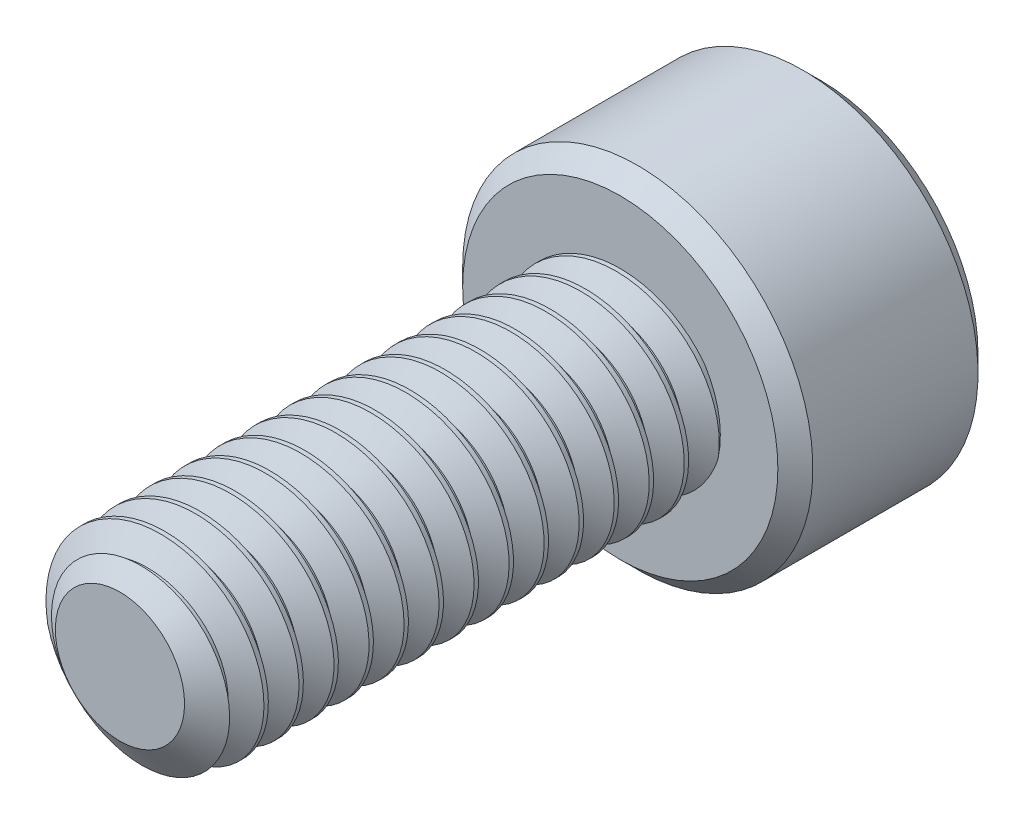
SolidWorks part; units mm, degrees
ref_plane "Front Plane" through (0, 0, 0) normal (0, 0, 1) x (1, 0, 0)
ref_plane "Top Plane" through (0, 0, 0) normal (0, 1, 0) x (1, 0, 0)
ref_plane "Right Plane" through (0, 0, 0) normal (1, 0, 0) x (0, 0, -1)
sketch "Sketch1" plane through (0, 0, 0) normal (0, 0, 1) x (1, 0, 0)
  circle A0 centre (0, 0) radius 2
  dimension "OD" = 4
extrude "Extrude1" add sketch "Sketch1" against normal blind 10
sketch "Sketch2" plane through (0, 0, 0) normal (0, 0, 1) x (1, 0, 0)
  circle A0 centre (0, 0) radius 2 construction
  circle A1 centre (0, 0) radius 2
curve "Helix/Spiral1" pitch 0.7 height 10.7 radius 2 centre (0, 0, 0) axis (0, 0, -1) start towards (0, 1, 0) parameters "pitch"=0.7
sketch "Sketch3" plane through (0, 0, 0) normal (1, 0, 0) x (0, 0, -1)
  line L0 (-0.6125, 2) -> (-0.35, 1.5453)
  line L1 (-0.35, 1.5453) -> (-0.2625, 1.5453)
  line L2 (-0.2625, 1.5453) -> (0, 2)
  line L3 (-0.6125, 2) -> (0, 2)
  line L4 (-0.3063, 2) -> (-0.3063, 1.5453) construction
  line L5 (-0.4813, 1.7727) -> (-0.1313, 1.7727) construction
  line L6 (0, 2) -> (0, -2) construction
  dimension "D1" = 0.0875
  dimension "D2" = 0.35
  dimension "D3" = 60
sweep "Cut-Sweep1" cut profiles "Sketch3" path "Helix/Spiral1"
sketch "Sketch4" plane through (0, 0, 0) normal (1, 0, 0) x (0, 0, -1)
  line L0 (0.4962, 2) -> (0, 1.2913)
  line L1 (0, 1.2913) -> (0, 2)
  line L2 (0.4962, 2) -> (0, 2)
  line L3 (-0.6125, 2) -> (0, 2) construction
  line L4 (0, 0) -> (7.0209, 0) construction
  dimension "D1" = 55
  dimension "D2" = 0.254
revolve "Cut-Revolve1" cut sketch "Sketch4" angle 360 about L4
sketch "Sketch6" plane through (0, 0, -10) normal (0, 0, -1) x (-1, 0, 0)
  circle A0 centre (0, 0) radius 3.5
  dimension "head dia" = 7
extrude "Extrude2" add sketch "Sketch6" along normal blind 4
sketch "Sketch7" plane through (0, 0, -14) normal (0, 0, -1) x (-1, 0, 0)
  line L1 (0, 1.7321) -> (-1.5, 0.866)
  line L2 (-1.5, 0.866) -> (-1.5, -0.866)
  line L3 (-1.5, -0.866) -> (0, -1.7321)
  line L4 (0, -1.7321) -> (1.5, -0.866)
  line L5 (1.5, -0.866) -> (1.5, 0.866)
  line L6 (1.5, 0.866) -> (0, 1.7321)
  circle A0 centre (0, 0) radius 1.5 construction
  dimension "hex dia" = 3
extrude "Cut-Extrude1" cut sketch "Sketch7" against normal blind 2.25
sketch "Sketch8" plane through (0, 0, -14) normal (0, 0, -1) x (-1, 0, 0)
  circle A0 centre (0, 0) radius 1.7321
extrude "Cut-Extrude2" cut sketch "Sketch8" against normal through all draft 45
chamfer "Chamfer1" distance 0.35 angle 45 2 edges at (-3.5, 0, -14) (-3.5, 0, -10)
sketch "Sketch10" plane through (0, 0, -10) normal (0, 0, 1) x (1, 0, 0)
  circle A1 centre (0, 0) radius 2
  circle A2 centre (0, 0) radius 2
  dimension "D1" = 0
ref_plane "Plane1" through (0, 0, 0) normal (0, 0, 1) x (1, 0, 0)
extrude "partial thread" [suppressed] add sketch "Sketch10" along normal up to surface (36 mm away) separate body up to plane "Plane1"
chamfer "Chamfer2" [suppressed] distance 0.08 angle 45
combine bodies "Combine1" [suppressed] operation type add bodies to combine 107 108
sketch "Sketch9" plane through (0, 0, 0) normal (1, 0, 0) x (0, 0, -1)
  line L0 (0, 2) -> (0, -2) construction
  line L1 (1.75, 2) -> (1.75, -2) construction
  dimension "D1" = 1.75
equation "\"D3@Helix/Spiral1\" = \"screw length@Extrude1\"+\"pitch@Helix/Spiral1\""
equation "\"D1@Sketch3\" = \"pitch@Helix/Spiral1\"*.125"
equation "\"D2@Sketch3\" = \"pitch@Helix/Spiral1\"*.5"
equation "\"D1@Cut-Extrude1\" = \"hex dia@Sketch7\"*.75"
equation "\"D1@Chamfer1\" = \"head dia@Sketch6\"*.05"
equation "\"D1@Sketch9\" = \"pitch@Helix/Spiral1\"*2.5"
equation "\"D1@Chamfer2\"=\"OD@Sketch1\"*.02"
